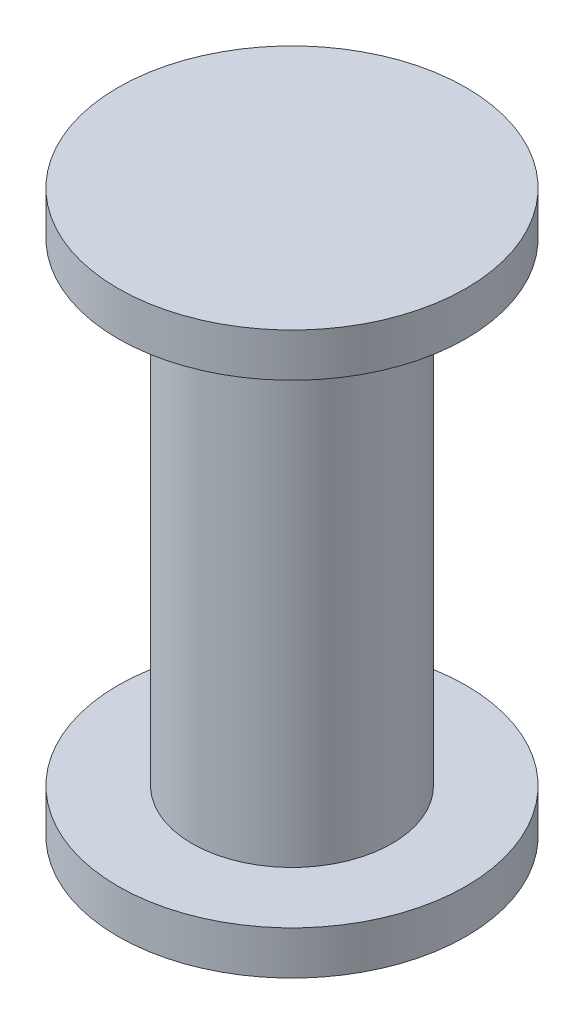
SolidWorks part; units mm, degrees
ref_plane "Front Plane" through (0, 0, 0) normal (0, 0, 1) x (1, 0, 0)
ref_plane "Top Plane" through (0, 0, 0) normal (0, 1, 0) x (1, 0, 0)
ref_plane "Right Plane" through (0, 0, 0) normal (1, 0, 0) x (0, 0, -1)
sketch "Sketch1" plane through (0, 0, 0) normal (0, 1, 0) x (1, 0, 0)
  circle A0 centre (0, 0) radius 2.3
  dimension "D1" = 4.6
extrude "Boss-Extrude1" add sketch "Sketch1" along normal blind 12.9
ref_plane "Plane1" through (0, 6.45, 0) normal (0, 1, 0) x (1, 0, 0)
sketch "Sketch2" plane through (0, 6.45, 0) normal (0, 1, 0) x (1, 0, 0)
  circle A0 centre (0, 0) radius 2.3
  circle A1 centre (0, 0) radius 4
  circle A2 centre (0, 0) radius 2.3 construction
  dimension "D1" = 8
extrude "Boss-Extrude2" add sketch "Sketch2" against normal blind 1 from surface starting at face at (0, 12.9, 2.3)
extrude "Boss-Extrude3" add sketch "Sketch2<3>" along normal blind 1 from surface starting at face at (0, 0, 2.3)
sketch "Sketch2<3>" plane through (0, 6.45, 0) normal (0, 1, 0) x (1, 0, 0) same geometry as "Sketch2"
